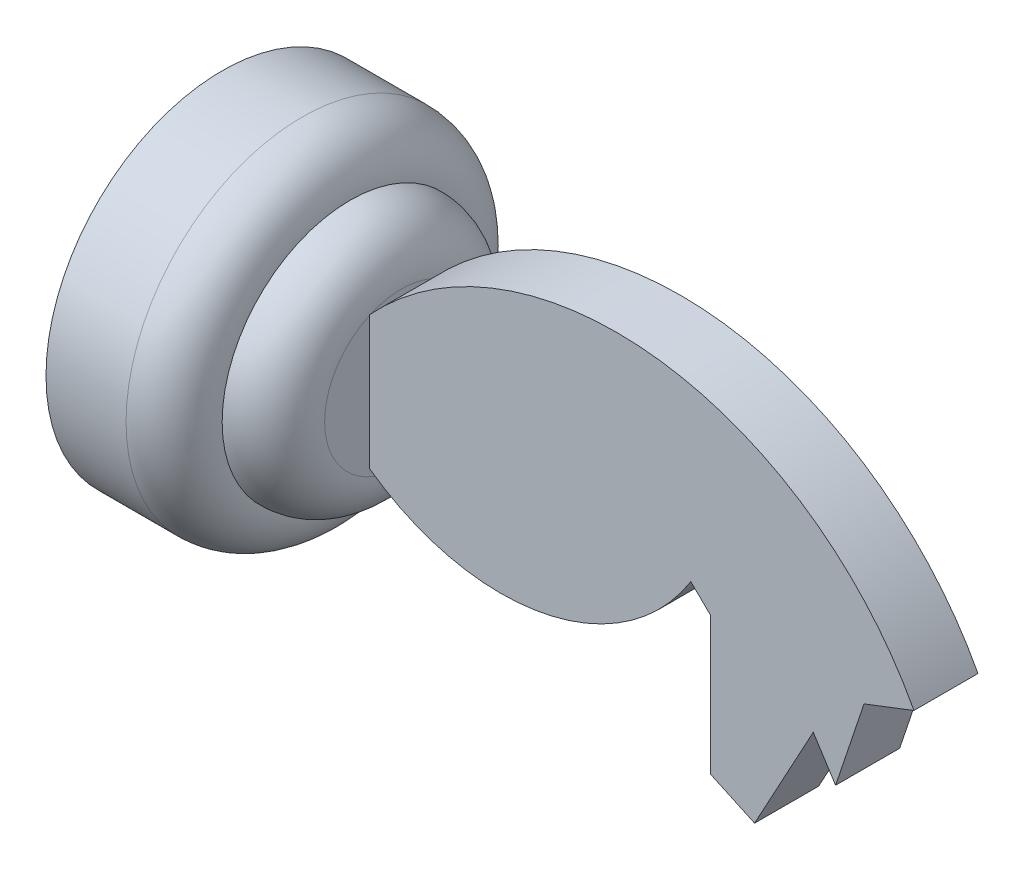
SolidWorks part; units mm, degrees
ref_plane "Спереди" through (0, 0, 0) normal (0, 0, 1) x (1, 0, 0)
ref_plane "Сверху" through (0, 0, 0) normal (0, 1, 0) x (1, 0, 0)
ref_plane "Справа" through (0, 0, 0) normal (1, 0, 0) x (0, 0, -1)
other "Configuration Table"
sketch "Эскиз1" plane through (0, 0, 0) normal (0, 0, 1) x (1, 0, 0)
  line L0 (0, 0) -> (71.2267, 0) construction
sketch "попа" plane through (0, 0, 0) normal (0, 0, 1) x (1, 0, 0)
  line L0 (0, 0) -> (0, 11)
  line L3 (0, 0) -> (71.2267, 0) construction
  line L7 (11.2, 4.8) -> (11.2, 0)
  line L8 (11.2, 0) -> (0, 0)
  line L9 (8, 0) -> (8, 8)
  line L10 (11.2, 0.68) -> (11.2, 0)
  line L12 (11.2, 0) -> (45.2, 0)
  line L16 (1, 0) -> (3.5, 0)
  line L17 (1, 0) -> (1, 5.25)
  line L18 (1, 5.25) -> (3.5, 5.25)
  line L19 (3.5, 5.25) -> (3.5, 0)
  line L20 (0, 11) -> (5, 11)
  line L21 (5, 11) -> (5, 0)
  arc A0 (5, 11) -> (8, 8) centre (5, 8) cw
  arc A1 (11.2, 4.8) -> (8, 8) centre (8, 4.8) ccw
  point P4 (11.2, 3.2539)
  point P15 (0, 0)
  point P17 (0, 0)
  point P20 (11.2, -6.4331)
  point P21 (0, 0)
  point P23 (0, 0)
  point P24 (11.2, 2.4)
  point P26 (0, 0)
  point P27 (11.2, 2.4)
  point P28 (0, 0)
  point P29 (0, 0)
  point P30 (0, 0)
  point P31 (11.2, 2.6832)
  point P32 (11.2, 3.1393)
  point P33 (11.2, 3.5661)
  point P34 (11.2, 0.682)
  point P35 (0, 0)
  point P36 (0, 0)
  point P37 (0, 0)
  point P38 (0, 0)
  point P39 (0, 0)
  point P40 (11.2, 0.68)
  point P41 (0, 0)
  point P42 (0, 0)
  point P43 (0, 0)
  point P44 (0, 0)
  point P45 (0, 0)
  point P46 (0, 0)
  dimension "D6" = 3
  dimension "D7" = 3.2
  dimension "D9" = 5.25
  dimension "D10" = 2.5
  dimension "D12" = 0.68
  dimension "D13" = 5.75
  dimension "D1" = 8
  dimension "D2" = 5
  dimension "D3" = 11.2
  dimension "D4" = 4.8
  dimension "D5" = 8
  dimension "D8" = 1
  dimension "D11" = 11
revolve "Повернуть1" add sketch "попа" angle 360 about L0 region at (2.5784, 6.4011, 0) region at (2.25, 2.625, 0) region at (6.4484, 5.1997, 0) region at (9.5169, 3.6915, 0)
sketch "вверх" plane through (0, 0, 0) normal (0, 0, 1) x (1, 0, 0)
  line L0 (11.2, 0) -> (11.2, 4.4)
  line L1 (11.2, -4.8) -> (11.2, 4.8) construction
  line L2 (11.2, 0) -> (45.2, 0)
  line L3 (0, 0) -> (71.2267, 0) construction
  line L5 (11.2, 0) -> (11.2, -3.915)
  line L6 (42.083, -1.2) -> (42.083, 0)
  line L7 (40.3075, -6.49) -> (40.3075, 0)
  line L8 (38.912, -4.32) -> (38.912, 0)
  line L9 (31.2635, 0) -> (32.499, -1.1973)
  line L10 (32.499, -1.1973) -> (32.499, -9.7973)
  line L11 (32.499, -9.7973) -> (35.2487, -11.07)
  line L12 (35.2487, -11.07) -> (38.912, -4.32)
  line L13 (38.912, -4.32) -> (40.3075, -6.49)
  line L14 (40.3075, -6.49) -> (42.083, -1.2)
  line L15 (42.083, -1.2) -> (45.2, 0)
  line L16 (35.2487, -11.07) -> (35.2487, 0)
  arc A1 (31.2635, 0) -> (11.2, -3.915) centre (19.3994, 7.4327) cw
  arc A2 (11.2, 4.4) -> (45.2, 0) centre (26.6431, -9.8306) cw
  dimension "D3" = 21
  dimension "D6" = 14
  dimension "D7" = 8.6
  dimension "D1" = 4.4
  dimension "D2" = 34
  dimension "D4" = 20.0635
  dimension "D5" = 3.915
  dimension "D8" = 1.7204
  dimension "D9" = 3.03
  dimension "D10" = 7.68
  dimension "D11" = 2.58
  dimension "D12" = 5.58
  dimension "D13" = 3.34
  dimension "D14" = 13.9365
  dimension "D15" = 1.2
  dimension "D16" = 6.49
  dimension "D17" = 4.32
  dimension "D18" = 11.07
extrude "верх" add sketch "вверх" along normal mid plane 4 contours A2 L0 L2 | A1 L2 L5 | L16 L12 L8 L2 | L11 L16 L2 L9 L10 | L7 L14 L6 L2 | L8 L13 L7 L2 | L6 L15 L2 region at (27.0721, 4.6677, 0) region at (20.1547, -2.7915, 0) region at (33.8562, -5.102, 0) region at (43.122, -0.4, 0) region at (36.8126, -4.0942, 0) region at (40.9917, -2.2258, 0) region at (39.6565, -2.7388, 0)
revolve "Повернуть2" add sketch "попа<16>" angle 360 about L0 region at (6.4484, 5.1997, 0)
sketch "попа<16>" plane through (0, 0, 0) normal (0, 0, 1) x (1, 0, 0) same geometry as "попа"
